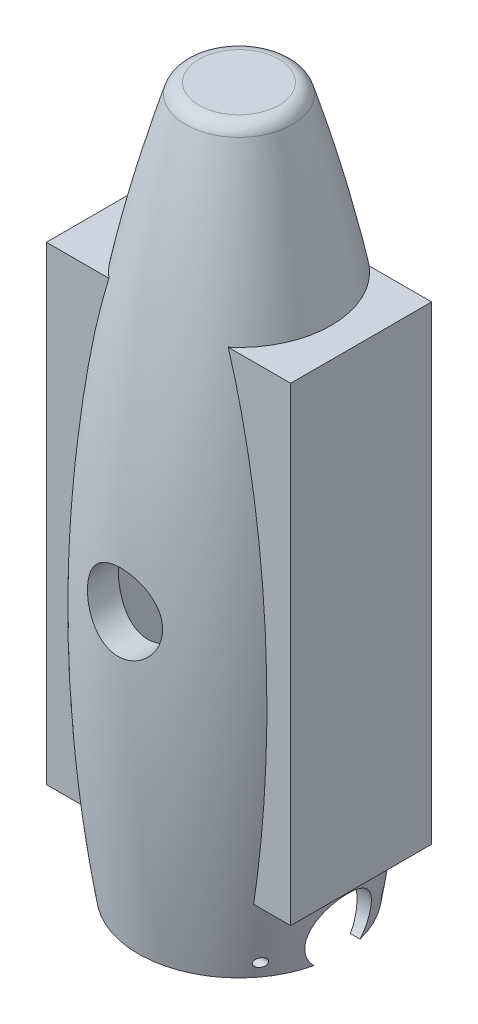
SolidWorks part; units mm, degrees
ref_plane "Front Plane" through (0, 0, 0) normal (0, 0, 1) x (1, 0, 0)
ref_plane "Top Plane" through (0, 0, 0) normal (0, 1, 0) x (1, 0, 0)
ref_plane "Right Plane" through (0, 0, 0) normal (1, 0, 0) x (0, 0, -1)
sketch "Sketch2" plane through (0, 0, 0) normal (0, 0, 1) x (1, 0, 0)
  line L0 (0, 145) -> (0, -5) construction
  line L1 (0, 145) -> (0, -5)
  line L2 (21.4243, -5) -> (0, -5)
  line L3 (0, 145) -> (21.4243, 145) construction
  line L5 (0, 145) -> (10.7121, 145)
  spline S1 degree 2 poles (10.7121, 145) (33.8436, 71.2518) (21.4243, -5) knots 0 0 0 1 1 1
  point P0 (21.4243, -5)
  point P2 (0, 145)
  point P9 (21.4243, 145)
  point P12 (10.7121, 145)
  point P14 (0, 70)
  point P16 (25, 70)
  dimension "D1" = 22
  dimension "D2" = 150
  dimension "D3" = 5
  dimension "D4" = 25
ref_axis "Central Axis" through (0, 157.5, 0) along (0, -1, 0)
revolve "Main Body" add sketch "Sketch2" angle 360 about L1
fillet "Fillet on Top Edge" radius 3 1 edges at (0, 145, 10.7121)
sketch "Sketch4" plane through (0, 145, 0) normal (0, 1, 0) x (1, 0, 0)
  circle A0 centre (0, 0) radius 8
  dimension "D1" = 16
extrude "Cut for Top Button" [suppressed] cut sketch "Sketch4" against normal up to next
sketch "Sketch7" plane through (0, 0, 0) normal (1, 0, 0) x (0, 0, -1)
  circle A0 centre (0, 0) radius 7
  dimension "D1" = 14
extrude "Cut for Wires" cut sketch "Sketch7" along normal through all
sketch "Sketch8" plane through (0, -5, 0) normal (0, -1, 0) x (1, 0, 0)
  circle A0 centre (0, 0) radius 19.4243
  circle A1 centre (0, 0) radius 21.4243 construction
  dimension "D1" = 2
extrude "Cut for Hollow Inside" cut sketch "Sketch8" against normal blind 105
sketch "Sketch9" plane through (0, 0, 0) normal (0, 0, 1) x (1, 0, 0)
  line L0 (0, 157.5) -> (0, -7.5) construction
  circle A0 centre (0, 60) radius 8
  dimension "D1" = 16
  dimension "D2" = 60
extrude "Cut for Side Button" cut sketch "Sketch9" along normal through all
ref_plane "Left Side" through (26, 0, 0) normal (1, 0, 0) x (0, 0, -1)
ref_plane "Right Side" through (-26, 0, 0) normal (1, 0, 0) x (0, 0, -1)
sketch "Sketch10" plane through (-26, 0, 0) normal (1, 0, 0) x (0, 0, -1)
  line L0 (-19.4243, -5) -> (19.4243, -5) construction
  line L1 (-15, 10) -> (15, 10)
  line L2 (-15, 10) -> (-15, 110)
  line L3 (-15, 110) -> (15, 110)
  line L4 (15, 10) -> (15, 110)
  line L5 (-15, 10) -> (15, 110) construction
  line L6 (-15, 110) -> (15, 10) construction
  point P0 (0, 60)
  point P5 (0, -5)
  dimension "D1" = 65
  dimension "D2" = 100
  dimension "D3" = 30
extrude "Right PCB Plate" add sketch "Sketch10" along normal up to next
mirror "Left PCB Plate" about plane through (0, 0, 0) normal (1, 0, 0) of "Right PCB Plate"
sketch "Sketch11" plane through (0, 0, 0) normal (1, 0, 0) x (0, 0, -1)
  line L0 (0, 157.5) -> (0, -7.5) construction
  circle A0 centre (-13, -2) radius 1
  circle A1 centre (13, -2) radius 1
  point P0 (13, 0)
  point P1 (13, -2)
  point P4 (-13, -2)
  dimension "D4" = 2
  dimension "D5" = 2
  dimension "D1" = 13
  dimension "D2" = 2
  dimension "D3" = 13
extrude "Cuts for Body Screw Holes" cut sketch "Sketch11" against normal through all both and the other way through all
